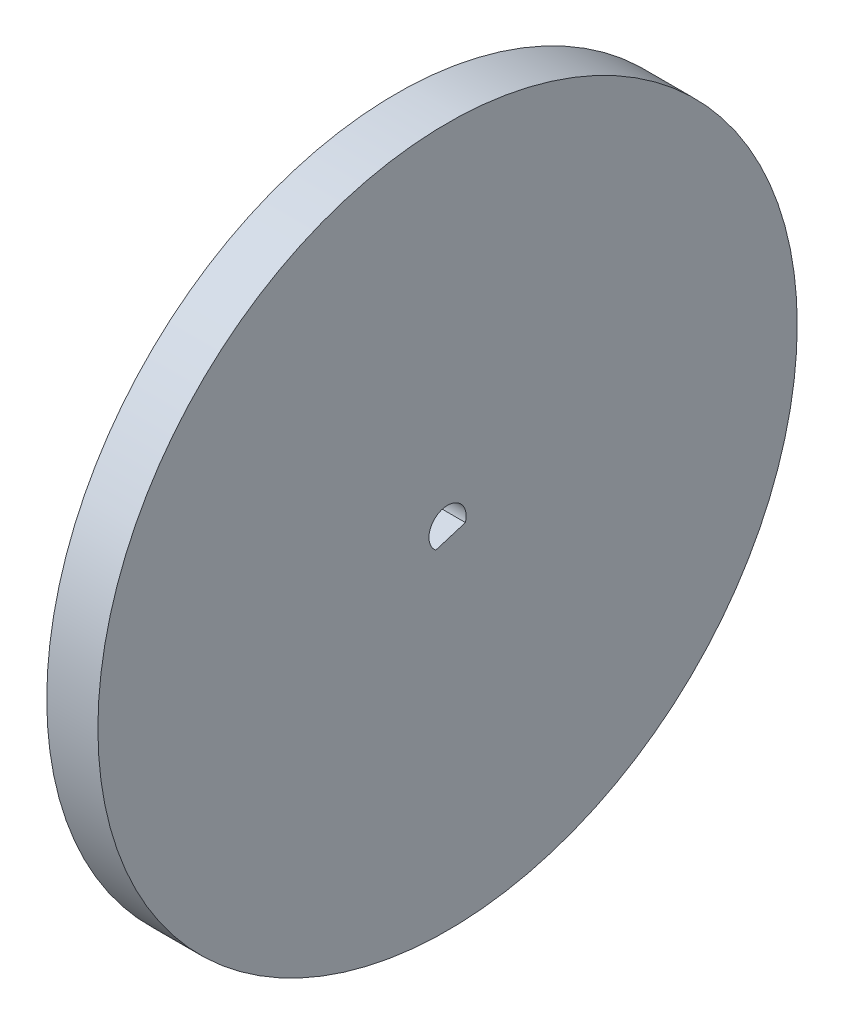
SolidWorks part; units mm, degrees
ref_plane "Front Plane" through (0, 0, 0) normal (0, 0, 1) x (1, 0, 0)
ref_plane "Top Plane" through (0, 0, 0) normal (0, 1, 0) x (1, 0, 0)
ref_plane "Right Plane" through (0, 0, 0) normal (1, 0, 0) x (0, 0, -1)
sketch "Sketch1" plane through (0, 0, 0) normal (1, 0, 0) x (0, 0, -1)
  circle A0 centre (0, 0) radius 43.434
  dimension "D1" = 86.868
extrude "Boss-Extrude1" add sketch "Sketch1" along normal blind 6.35
sketch "Sketch5" plane through (6.35, 0, 0) normal (1, 0, 0) x (0, 0, -1)
  line L1 (-1.4673, -1.7859) -> (2.2167, -0.6548)
  arc A3 (2.2167, -0.6548) -> (-1.4673, -1.7859) centre (0, 0) ccw
  dimension "D1" = 2.3114
  dimension "D2" = 3.6841
extrude "Cut-Extrude1" cut sketch "Sketch5" against normal through all
